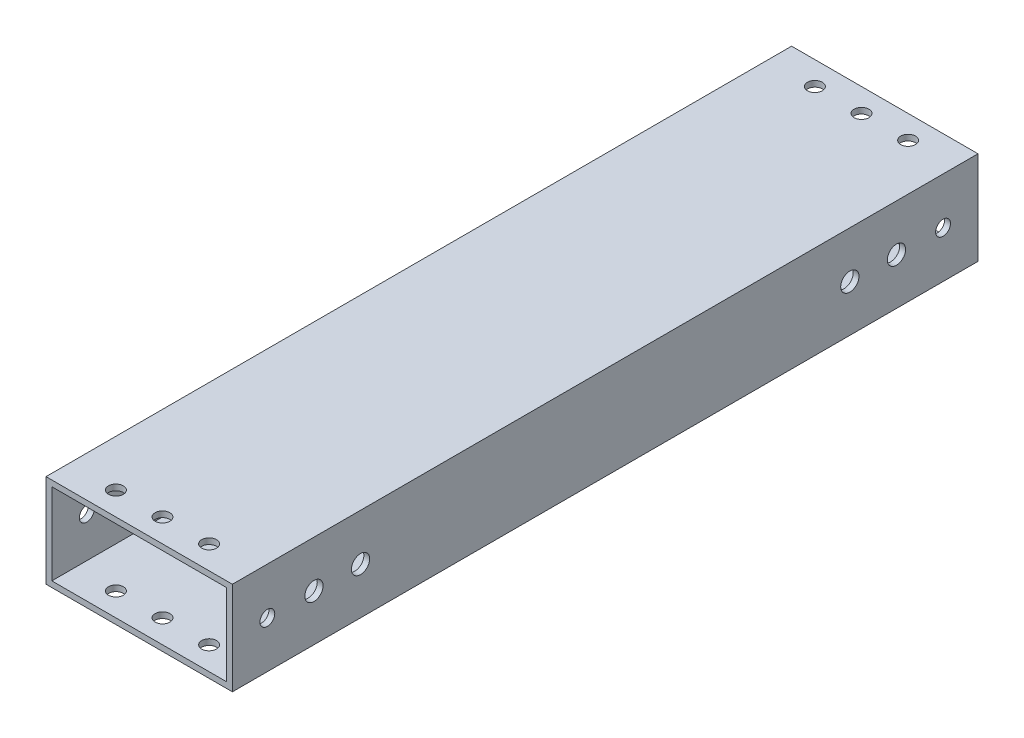
SolidWorks part; units mm, degrees
material "6061-T6 (SS)"
ref_plane "Front Plane" through (0, 0, 0) normal (0, 0, 1) x (1, 0, 0)
ref_plane "Top Plane" through (0, 0, 0) normal (0, 1, 0) x (1, 0, 0)
ref_plane "Right Plane" through (0, 0, 0) normal (1, 0, 0) x (0, 0, -1)
sketch "Sketch1" plane through (0, 0, 0) normal (0, 0, 1) x (1, 0, 0)
  line L0 (-23.8125, 11.1125) -> (23.8125, 11.1125)
  line L1 (-25.4, -12.7) -> (25.4, -12.7)
  line L2 (-25.4, -12.7) -> (-25.4, 12.7)
  line L3 (-25.4, 12.7) -> (25.4, 12.7)
  line L4 (25.4, -12.7) -> (25.4, 12.7)
  line L5 (-25.4, -12.7) -> (25.4, 12.7) construction
  line L6 (-25.4, 12.7) -> (25.4, -12.7) construction
  line L7 (23.8125, -11.1125) -> (23.8125, 11.1125)
  line L8 (-23.8125, -11.1125) -> (23.8125, -11.1125)
  line L9 (-23.8125, -11.1125) -> (-23.8125, 11.1125)
  point P0 (0, 0)
  dimension "D1" = 50.8
  dimension "D2" = 25.4
  dimension "D3" = 1.5875
extrude "Boss-Extrude1" add sketch "Sketch1" along normal mid plane 203.2
sketch "Sketch2" plane through (25.4, 0, 0) normal (1, 0, 0) x (0, 0, -1)
  line L0 (-101.6, -12.7) -> (-101.6, 12.7) construction
  line L1 (0, 12.7) -> (0, -12.7) construction
  line L2 (-101.6, 12.7) -> (101.6, 12.7) construction
  line L3 (-101.6, -12.7) -> (101.6, -12.7) construction
  circle A0 centre (-92.075, 0) radius 2.0193
  circle A1 centre (92.075, 0) radius 2.0193
  circle A2 centre (-79.375, 0) radius 2.4892
  circle A3 centre (-66.675, 0) radius 2.4892
  circle A4 centre (66.675, 0) radius 2.4892
  circle A5 centre (79.375, 0) radius 2.4892
  point P17 (0, 0)
  dimension "D2" = 4.0386
  dimension "D5" = 4.9784
  dimension "D1" = 9.525
  dimension "D3" = 12.7
  dimension "D4" = 12.7
extrude "Cut-Extrude1" cut sketch "Sketch2" against normal through all
sketch "Sketch3" plane through (0, 12.7, 0) normal (0, 1, 0) x (1, 0, 0)
  line L0 (-25.4, 0) -> (25.4, 0) construction
  line L1 (-25.4, -101.6) -> (-25.4, 101.6) construction
  line L2 (25.4, -101.6) -> (25.4, 101.6) construction
  line L3 (25.4, -101.6) -> (-25.4, -101.6) construction
  circle A0 centre (-12.7, -95.25) radius 2.0193
  circle A1 centre (0, -95.25) radius 2.0193
  circle A2 centre (12.7, -95.25) radius 2.0193
  circle A3 centre (12.7, 95.25) radius 2.0193
  circle A4 centre (0, 95.25) radius 2.0193
  circle A5 centre (-12.7, 95.25) radius 2.0193
  dimension "D1" = 4.0386
  dimension "D2" = 12.7
  dimension "D3" = 12.7
  dimension "D4" = 6.35
extrude "Cut-Extrude2" cut sketch "Sketch3" against normal through all
